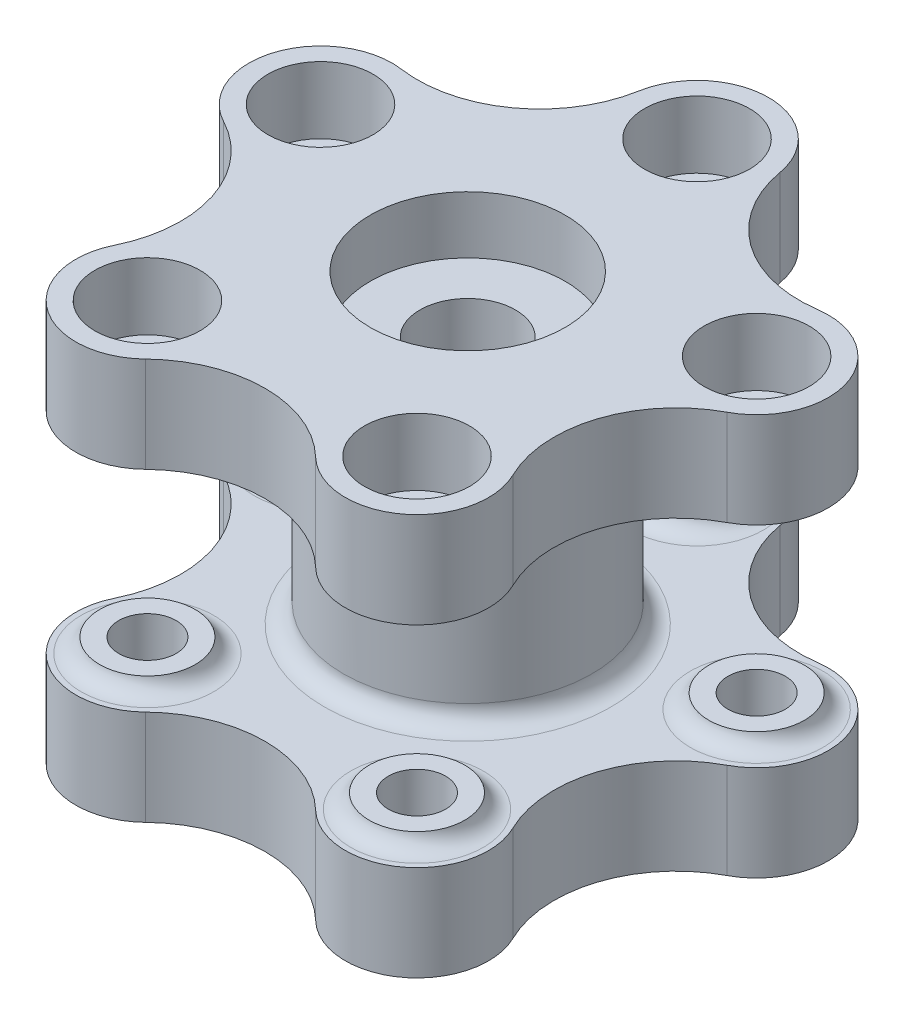
SolidWorks part; units mm, degrees
ref_plane "Front Plane" through (0, 0, 0) normal (0, 0, 1) x (1, 0, 0)
ref_plane "Top Plane" through (0, 0, 0) normal (0, 1, 0) x (1, 0, 0)
ref_plane "Right Plane" through (0, 0, 0) normal (1, 0, 0) x (0, 0, -1)
sketch "Sketch1" plane through (0, 0, 0) normal (0, 1, 0) x (1, 0, 0)
  line L0 (-15.75, 15.75) -> (15.75, 15.75) construction
  line L1 (7.0534, -9.7082) -> (11.4127, 3.7082) construction
  line L2 (11.4127, 3.7082) -> (0, 12) construction
  line L3 (0, 12) -> (-11.4127, 3.7082) construction
  line L4 (-11.4127, 3.7082) -> (-7.0534, -9.7082) construction
  line L5 (-7.0534, -9.7082) -> (7.0534, -9.7082) construction
  line L6 (-15.75, 0) -> (-15.75, 15.75) construction
  line L7 (15.75, 0) -> (15.75, 15.75) construction
  line L8 (-15.75, 13.5) -> (15.75, 13.5) construction
  line L9 (-6.2335, 8.5796) -> (-9.9923, 13.7533) construction
  line L10 (-1.4309, -2.05) -> (1.4309, -2.05)
  arc A0 (-14.9791, 4.867) -> (14.9791, 4.867) centre (0, 0) ccw construction
  arc A1 (1.4309, -2.05) -> (-1.4309, -2.05) centre (0, 0) ccw
  circle A2 centre (0, 0) radius 9.7082 construction
  circle A3 centre (0, 12) radius 1.5
  circle A4 centre (11.4127, 3.7082) radius 1.5
  circle A5 centre (7.0534, -9.7082) radius 1.5
  circle A6 centre (-7.0534, -9.7082) radius 1.5
  circle A7 centre (-11.4127, 3.7082) radius 1.5
  circle A8 centre (0, 12) radius 5 construction
  arc A9 (-10.8877, 7.4213) -> (-3.6936, 12.6481) centre (-9.9923, 13.7533) ccw
  arc A10 (-10.8877, 7.4213) -> (-14.9791, 4.867) centre (-11.4127, 3.7082) ccw
  arc A12 (3.6936, 12.6481) -> (-3.6936, 12.6481) centre (0, 12) ccw
  arc A13 (3.6936, 12.6481) -> (10.8877, 7.4213) centre (9.9923, 13.7533) ccw
  arc A14 (13.1704, 0.3957) -> (10.4225, -8.0615) centre (16.168, -5.2533) ccw
  arc A15 (4.4462, -12.4035) -> (-4.4462, -12.4035) centre (0, -17) ccw
  arc A16 (-10.4225, -8.0615) -> (-13.1704, 0.3957) centre (-16.168, -5.2533) ccw
  arc A20 (-13.1704, 0.3957) -> (-14.9791, 4.867) centre (-11.4127, 3.7082) cw
  arc A21 (4.4462, -12.4035) -> (10.4225, -8.0615) centre (7.0534, -9.7082) ccw
  arc A22 (13.1704, 0.3957) -> (10.8877, 7.4213) centre (11.4127, 3.7082) ccw
  circle A23 centre (7.0534, -9.7082) radius 5 construction
  arc A24 (-10.4225, -8.0615) -> (-4.4462, -12.4035) centre (-7.0534, -9.7082) ccw
  circle A25 centre (0, 0) radius 17 construction
  point P43 (0, 0)
  dimension "D1" = 31.5
  dimension "D2" = 5
  dimension "D3" = 3
  dimension "D4" = 10
  dimension "D5" = 10
  dimension "D6" = 5
  dimension "D7" = 2.05
  dimension "D8" = 34
extrude "Boss-Extrude1" add sketch "Sketch1" along normal blind 5
sketch "Sketch2" plane through (0, 5, 0) normal (0, 1, 0) x (1, 0, 0)
  line L0 (-1.4309, -2.05) -> (1.4309, -2.05) construction
  line L1 (-1.4309, -2.05) -> (1.4309, -2.05)
  circle A0 centre (0, 0) radius 6.5
  circle A2 centre (0, 12) radius 5 construction
  arc A3 (1.4309, -2.05) -> (-1.4309, -2.05) centre (0, 0) ccw construction
  arc A4 (1.4309, -2.05) -> (-1.4309, -2.05) centre (0, 0) ccw
  dimension "D1" = 13
  dimension "D3" = 10
extrude "Boss-Extrude2" add sketch "Sketch2" along normal blind 11
sketch "Sketch3" plane through (0, 16, 0) normal (0, 1, 0) x (1, 0, 0)
  line L0 (-1.4309, -2.05) -> (1.4309, -2.05) construction
  line L1 (-1.4309, -2.05) -> (1.4309, -2.05)
  circle A1 centre (-7.0534, -9.7082) radius 1.5 construction
  circle A14 centre (7.0534, -9.7082) radius 1.5 construction
  circle A15 centre (11.4127, 3.7082) radius 1.5 construction
  circle A16 centre (-11.4127, 3.7082) radius 1.5 construction
  circle A17 centre (0, 12) radius 1.5 construction
  circle A18 centre (-7.0534, -9.7082) radius 1.5
  circle A19 centre (7.0534, -9.7082) radius 1.5
  circle A20 centre (11.4127, 3.7082) radius 1.5
  circle A21 centre (-11.4127, 3.7082) radius 1.5
  circle A22 centre (0, 12) radius 1.5
  arc A23 (3.6936, 12.6481) -> (-3.6936, 12.6481) centre (0, 12) ccw
  arc A24 (-10.8877, 7.4213) -> (-3.6936, 12.6481) centre (-9.9923, 13.7533) ccw
  arc A25 (-10.8877, 7.4213) -> (-13.1704, 0.3957) centre (-11.4127, 3.7082) ccw
  arc A26 (-10.4225, -8.0615) -> (-13.1704, 0.3957) centre (-16.168, -5.2533) ccw
  arc A27 (-10.4225, -8.0615) -> (-4.4462, -12.4035) centre (-7.0534, -9.7082) ccw
  arc A28 (4.4462, -12.4035) -> (-4.4462, -12.4035) centre (0, -17) ccw
  arc A29 (4.4462, -12.4035) -> (10.4225, -8.0615) centre (7.0534, -9.7082) ccw
  arc A30 (13.1704, 0.3957) -> (10.4225, -8.0615) centre (16.168, -5.2533) ccw
  arc A31 (13.1704, 0.3957) -> (10.8877, 7.4213) centre (11.4127, 3.7082) ccw
  arc A32 (3.6936, 12.6481) -> (10.8877, 7.4213) centre (9.9923, 13.7533) ccw
  arc A33 (3.6936, 12.6481) -> (-3.6936, 12.6481) centre (0, 12) ccw
  arc A34 (-10.8877, 7.4213) -> (-3.6936, 12.6481) centre (-9.9923, 13.7533) ccw
  arc A35 (-10.8877, 7.4213) -> (-13.1704, 0.3957) centre (-11.4127, 3.7082) ccw
  arc A36 (-10.4225, -8.0615) -> (-13.1704, 0.3957) centre (-16.168, -5.2533) ccw
  arc A37 (-10.4225, -8.0615) -> (-4.4462, -12.4035) centre (-7.0534, -9.7082) ccw
  arc A38 (4.4462, -12.4035) -> (-4.4462, -12.4035) centre (0, -17) ccw
  arc A39 (4.4462, -12.4035) -> (10.4225, -8.0615) centre (7.0534, -9.7082) ccw
  arc A40 (13.1704, 0.3957) -> (10.4225, -8.0615) centre (16.168, -5.2533) ccw
  arc A41 (13.1704, 0.3957) -> (10.8877, 7.4213) centre (11.4127, 3.7082) ccw
  arc A42 (3.6936, 12.6481) -> (10.8877, 7.4213) centre (9.9923, 13.7533) ccw
  arc A45 (1.4309, -2.05) -> (-1.4309, -2.05) centre (0, 0) ccw construction
  arc A46 (1.4309, -2.05) -> (-1.4309, -2.05) centre (0, 0) ccw
  dimension "D1" = 0
extrude "Boss-Extrude3" add sketch "Sketch3" along normal blind 5
sketch "Sketch4" plane through (0, 0, 0) normal (0, 0, 1) x (1, 0, 0)
  line L0 (0, 0) -> (0, 21) construction
  line L1 (-4.4462, 0) -> (4.4462, 0) construction
  line L2 (4.4462, 21) -> (-4.4462, 21) construction
  circle A0 centre (0, 10.5) radius 1.4
  dimension "D1" = 2.8
extrude "Cut-Extrude1" cut sketch "Sketch4" along normal through all
fillet "Fillet1" radius 1 2 edges at (0, 16, 6.5) (0, 5, 6.5)
sketch "Sketch6" plane through (0, 0, 0) normal (0, -1, 0) x (1, 0, 0)
  line L0 (-12.0729, -6.8142) -> (-9.0529, -5.833)
  line L17 (2.75, -13.5877) -> (2.75, -10.4123)
  line L18 (2.75, -10.4123) -> (0, -8.8246)
  line L19 (0, -8.8246) -> (-2.75, -10.4123)
  line L20 (-2.75, -10.4123) -> (-2.75, -13.5877)
  line L21 (-2.75, -13.5877) -> (0, -15.1754)
  line L22 (0, -15.1754) -> (2.75, -13.5877)
  line L23 (-9.0529, -5.833) -> (-8.3927, -2.7269)
  line L24 (-8.3927, -2.7269) -> (-10.7525, -0.6022)
  line L25 (-10.7525, -0.6022) -> (-13.7725, -1.5834)
  line L26 (-13.7725, -1.5834) -> (-14.4327, -4.6895)
  line L27 (-14.4327, -4.6895) -> (-12.0729, -6.8142)
  line L28 (-10.2115, 9.3763) -> (-8.345, 6.8073)
  line L29 (-8.345, 6.8073) -> (-5.187, 7.1392)
  line L30 (-5.187, 7.1392) -> (-3.8954, 10.0401)
  line L31 (-3.8954, 10.0401) -> (-5.7619, 12.6091)
  line L32 (-5.7619, 12.6091) -> (-8.9199, 12.2772)
  line L33 (-8.9199, 12.2772) -> (-10.2115, 9.3763)
  line L34 (5.7619, 12.6091) -> (3.8954, 10.0401)
  line L35 (3.8954, 10.0401) -> (5.187, 7.1392)
  line L36 (5.187, 7.1392) -> (8.345, 6.8073)
  line L37 (8.345, 6.8073) -> (10.2115, 9.3763)
  line L38 (10.2115, 9.3763) -> (8.9199, 12.2772)
  line L39 (8.9199, 12.2772) -> (5.7619, 12.6091)
  line L40 (13.7725, -1.5834) -> (10.7525, -0.6022)
  line L41 (10.7525, -0.6022) -> (8.3927, -2.7269)
  line L42 (8.3927, -2.7269) -> (9.0529, -5.833)
  line L43 (9.0529, -5.833) -> (12.0729, -6.8142)
  line L44 (12.0729, -6.8142) -> (14.4327, -4.6895)
  line L45 (14.4327, -4.6895) -> (13.7725, -1.5834)
  circle A0 centre (0, -12) radius 2.75 construction
  circle A2 centre (-11.4127, -3.7082) radius 2.75 construction
  circle A3 centre (-7.0534, 9.7082) radius 2.75 construction
  circle A4 centre (7.0534, 9.7082) radius 2.75 construction
  circle A5 centre (11.4127, -3.7082) radius 2.75 construction
  circle A6 centre (-11.4127, -3.7082) radius 1.5 construction
  point P45 (0, 0)
  dimension "D1" = 5.5
  dimension "D2" = 5
extrude "Cut-Extrude2" cut sketch "Sketch6" against normal blind 3
sketch "Sketch8" plane through (0, 5, 0) normal (0, 1, 0) x (1, 0, 0)
  circle A0 centre (-7.0534, -9.7082) radius 2.5
  circle A1 centre (-7.0534, -9.7082) radius 1.5 construction
  circle A2 centre (-7.0534, -9.7082) radius 1.5
  circle A3 centre (-11.4127, 3.7082) radius 2.5
  circle A4 centre (-11.4127, 3.7082) radius 1.5
  circle A5 centre (0, 12) radius 2.5
  circle A6 centre (0, 12) radius 1.5
  circle A7 centre (11.4127, 3.7082) radius 2.5
  circle A8 centre (11.4127, 3.7082) radius 1.5
  circle A9 centre (7.0534, -9.7082) radius 2.5
  circle A10 centre (7.0534, -9.7082) radius 1.5
  circle A11 centre (7.0534, -9.7082) radius 1.5 construction
  point P24 (0, 0)
  dimension "D1" = 5
  dimension "D2" = 5
extrude "Boss-Extrude5" add sketch "Sketch8" along normal blind 0.75
fillet "Fillet4" radius 1 5 edges at (-11.4127, 5, -1.2082) (0, 5, -9.5) (11.4127, 5, -1.2082) (7.0534, 5, 12.2082) (-7.0534, 5, 12.2082)
sketch "Sketch9" plane through (0, 16, 0) normal (0, -1, 0) x (1, 0, 0)
  circle A0 centre (0, -12) radius 2.5
  circle A1 centre (0, -12) radius 1.5 construction
  circle A2 centre (0, -12) radius 1.5
  circle A3 centre (-11.4127, -3.7082) radius 2.5
  circle A4 centre (-11.4127, -3.7082) radius 1.5
  circle A5 centre (-7.0534, 9.7082) radius 2.5
  circle A6 centre (-7.0534, 9.7082) radius 1.5
  circle A7 centre (7.0534, 9.7082) radius 2.5
  circle A8 centre (7.0534, 9.7082) radius 1.5
  circle A9 centre (11.4127, -3.7082) radius 2.5
  circle A10 centre (11.4127, -3.7082) radius 1.5
  circle A11 centre (11.4127, -3.7082) radius 1.5 construction
  point P25 (0, 0)
  dimension "D1" = 5
  dimension "D2" = 5
extrude "Boss-Extrude6" add sketch "Sketch9" along normal blind 0.75
fillet "Fillet5" radius 1 5 edges at (7.0534, 16, 12.2082) (-7.0534, 16, 12.2082) (-11.4127, 16, -1.2082) (0, 16, -9.5) (11.4127, 16, -1.2082)
sketch "Sketch12" plane through (0, 21, 0) normal (0, 1, 0) x (1, 0, 0)
  circle A0 centre (0, 12) radius 2.75
  circle A1 centre (11.4127, 3.7082) radius 2.75
  circle A2 centre (7.0534, -9.7082) radius 2.75
  circle A3 centre (-7.0534, -9.7082) radius 2.75
  circle A4 centre (-11.4127, 3.7082) radius 2.75
  point P13 (0, 0)
  dimension "D1" = 5.5
  dimension "D2" = 5
extrude "Cut-Extrude5" cut sketch "Sketch12" against normal offset from surface (3.5 mm away) 1.5 up to face at (7.0534, 16, 13.1764)
sketch "Sketch10" plane through (0, 21, 0) normal (0, 1, 0) x (1, 0, 0)
  circle A0 centre (0, 0) radius 5.1
  dimension "D1" = 10.2
extrude "Cut-Extrude3" cut sketch "Sketch10" against normal blind 3
sketch "Sketch11" plane through (0, 0, 0) normal (0, -1, 0) x (1, 0, 0)
  circle A0 centre (0, 0) radius 5.1
  dimension "D1" = 10.2
extrude "Cut-Extrude4" cut sketch "Sketch11" against normal blind 3.5
